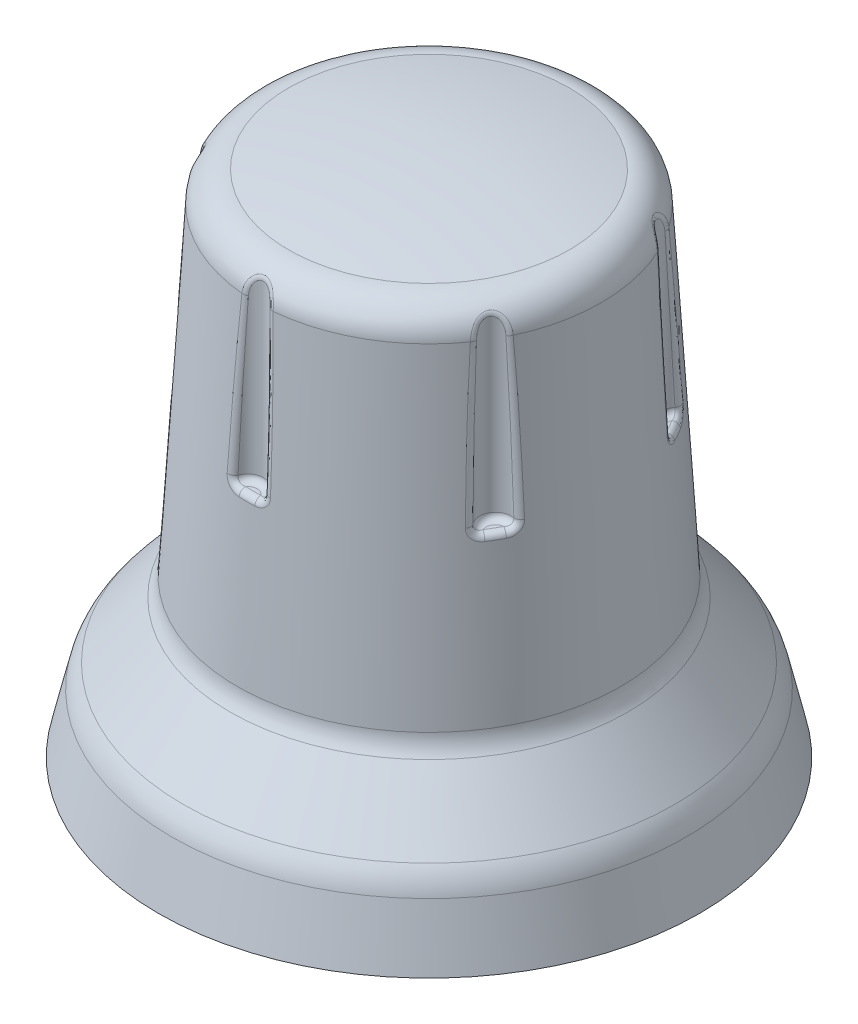
SolidWorks part; units mm, degrees
ref_plane "Piano frontale" through (0, 0, 0) normal (0, 0, 1) x (1, 0, 0)
ref_plane "Piano superiore" through (0, 0, 0) normal (0, 1, 0) x (1, 0, 0)
ref_plane "Piano destro" through (0, 0, 0) normal (1, 0, 0) x (0, 0, -1)
sketch "Schizzo1" plane through (0, 0, 0) normal (0, 0, 1) x (1, 0, 0)
  line L0 (0, 36.995) -> (0, -26.3642) construction
  line L1 (0, 0) -> (8.5, 0)
  line L2 (8.5, 0) -> (8.0707, 1.8594)
  line L3 (7.7176, 2.5727) -> (6.0365, 4.6)
  line L4 (6.0365, 4.6) -> (5.35, 16)
  line L5 (5.35, 16) -> (0, 16)
  line L6 (0, 16) -> (0, 0)
  arc A0 (7.7176, 2.5727) -> (8.0707, 1.8594) centre (6.3893, 1.4712) cw
  point P8 (7.7176, 2.5727)
  dimension "D1" = 16
  dimension "D2" = 10.7
  dimension "D3" = 17
  dimension "D4" = 4.6
  dimension "D5" = 283
revolve "Rivoluzione1" add sketch "Schizzo1" angle 360 about L0
fillet "Raccordo1" radius 1 1 edges at (0, 4.6, 6.0365)
fillet "Raccordo2" radius 1 1 edges at (0, 16, 5.35)
sketch "Schizzo2" plane through (0, 16, 0) normal (0, 1, 0) x (1, 0, 0)
  line L0 (0, 8.7158) -> (0, -1.4274) construction
  circle A0 centre (0, 5.7) radius 0.5
  circle A1 centre (4.9363, 2.85) radius 0.5
  circle A2 centre (4.9363, -2.85) radius 0.5
  circle A3 centre (0, -5.7) radius 0.5
  circle A4 centre (-4.9363, -2.85) radius 0.5
  circle A5 centre (-4.9363, 2.85) radius 0.5
  point P18 (0, 0)
  dimension "D2" = 1
  dimension "D1" = 5.7
  dimension "D3" = 6
extrude "Taglio-Estrusione1" cut sketch "Schizzo2" against normal blind 6
fillet "Raccordo3" radius 0.2 30 edges at (4.5032, 15.6111, 2.6001) (-0.0002, 15.6111, 5.2) (-4.5034, 15.6111, 2.5999) (-4.5032, 15.6111, -2.6001) (0.0002, 15.6111, -5.2) (4.5034, 15.6111, -2.5999) (4.9358, 14.0627, 2.35) (4.6278, 10.998, 3.2434) (0.4327, 14.0627, 5.4495) (-0.495, 10.998, 5.6295) (-4.5031, 14.0627, 3.0995) (-5.1228, 10.998, 2.3861) (-4.9358, 14.0627, -2.35) (-4.6278, 10.998, -3.2434) (-0.4327, 14.0627, -5.4495) (0.495, 10.998, -5.6295) (4.5031, 14.0627, -3.0995) (5.1228, 10.998, -2.3861) (4.5033, 10, 2.6) (4.9462, 10, 2.8557) (0, 10, 5.2) (0, 10, 5.7113) (-4.5033, 10, 2.6) (-4.9462, 10, 2.8557) (-4.5033, 10, -2.6) (-4.9462, 10, -2.8557) (0, 10, -5.2) (0, 10, -5.7113) (4.5033, 10, -2.6) (4.9462, 10, -2.8557)
dome "Cupola1" faces to dome 1 distance 0.4 reverse direction no elliptical dome no face at (0, 16, -4.4084) parameters "D1"=0.4
sketch "Schizzo3" plane through (0, 0, 0) normal (0, -1, 0) x (1, 0, 0)
  circle A0 centre (0, 0) radius 3
  dimension "D1" = 6
extrude "Taglio-Estrusione2" cut sketch "Schizzo3" against normal blind 6
